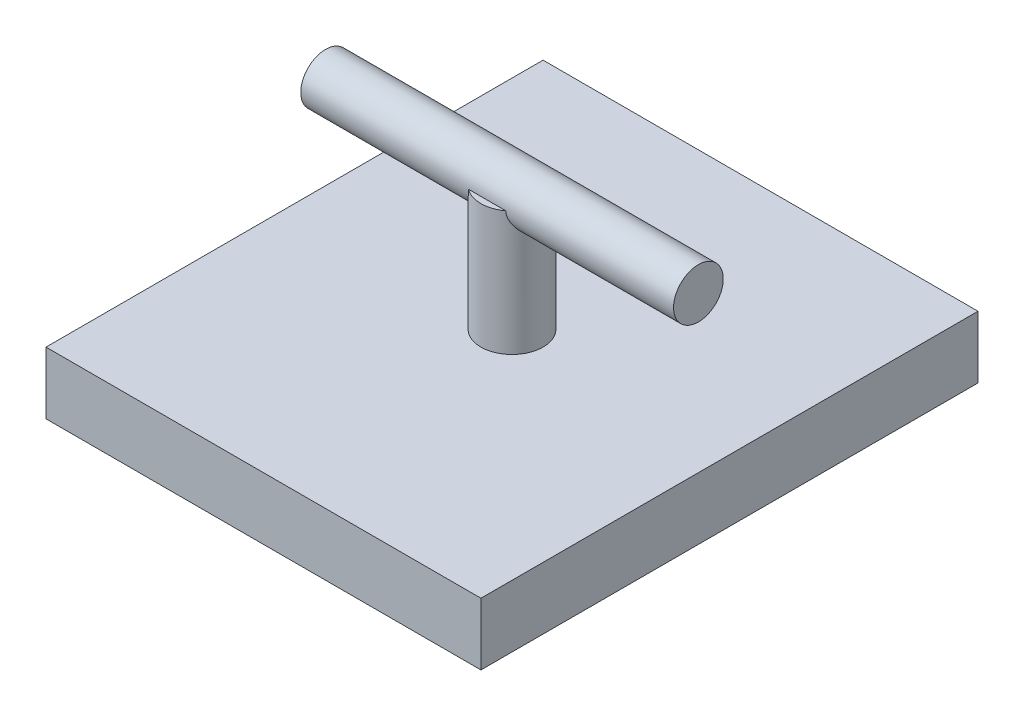
SolidWorks part; units mm, degrees
ref_plane "前视基准面" through (0, 0, 0) normal (0, 0, 1) x (1, 0, 0)
ref_plane "上视基准面" through (0, 0, 0) normal (0, 1, 0) x (1, 0, 0)
ref_plane "右视基准面" through (0, 0, 0) normal (1, 0, 0) x (0, 0, -1)
sketch "草图1" plane through (0, 0, 0) normal (0, 1, 0) x (1, 0, 0)
  line L0 (-30, 0) -> (30, 0)
  line L1 (-30, 4) -> (30, 4)
  line L2 (-30, 4) -> (-30, -4)
  line L3 (-30, -4) -> (30, -4)
  line L4 (30, 4) -> (30, -4)
  line L5 (-30, 4) -> (30, -4) construction
  line L6 (-30, -4) -> (30, 4) construction
  point P0 (0, 0)
revolve "旋转3" add sketch "草图1" angle 360 about L0 region at (0, 0, -2)
sketch "草图3" plane through (0, 0, 0) normal (0, 1, 0) x (1, 0, 0)
  circle A0 centre (0, 0) radius 5
extrude "凸台-拉伸2" add sketch "草图3" against normal blind 20
sketch "草图5" plane through (0, -20, 0) normal (0, -1, 0) x (1, 0, 0)
  line L1 (-35, 40) -> (35, 40)
  line L2 (-35, 40) -> (-35, -40)
  line L3 (-35, -40) -> (35, -40)
  line L4 (35, 40) -> (35, -40)
  line L5 (-35, 40) -> (35, -40) construction
  line L6 (-35, -40) -> (35, 40) construction
  point P0 (0, 0)
extrude "凸台-拉伸3" add sketch "草图5" along normal blind 10
